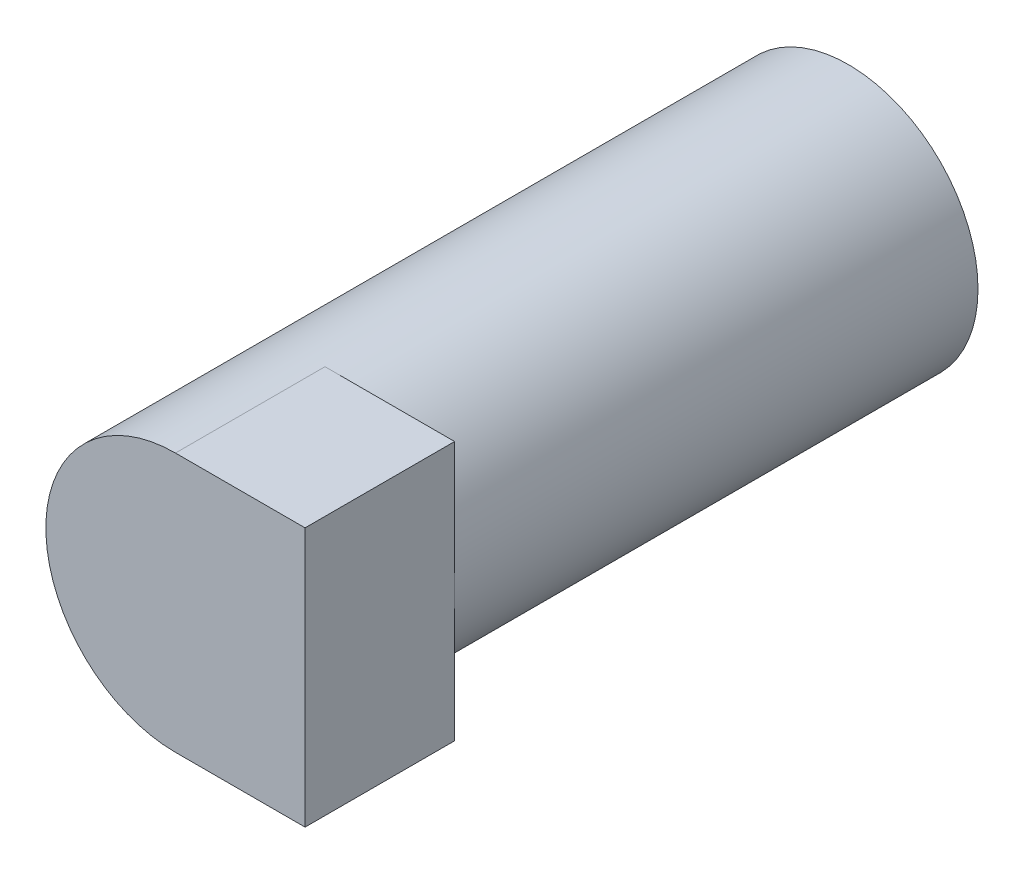
SolidWorks part; units mm, degrees
material "AISI 1045 Steel, cold drawn"
ref_plane "Front Plane" through (0, 0, 0) normal (0, 0, 1) x (1, 0, 0)
ref_plane "Top Plane" through (0, 0, 0) normal (0, 1, 0) x (1, 0, 0)
ref_plane "Right Plane" through (0, 0, 0) normal (1, 0, 0) x (0, 0, -1)
ref_axis "Axis1" through (0, 55, 0) along (0, -1, 0)
ref_axis "Axis2" through (88.99, 0, 0) along (-1, 0, 0)
ref_axis "Axis3" through (0, 0, -88.99) along (0, 0, 1)
sketch "Sketch1" plane through (0, 0, 0) normal (0, 0, 1) x (1, 0, 0)
  circle A0 centre (0, 0) radius 13
  dimension "D1" = 26
extrude "Boss-Extrude1" add sketch "Sketch1" along normal blind 67.5
sketch "Sketch2" plane through (0, 0, 0) normal (1, 0, 0) x (0, 0, -1)
  line L0 (-67.5, -13) -> (0, -13) construction
  line L1 (-67.5, 13) -> (-52.5, 13)
  line L2 (-67.5, 13) -> (-67.5, -13)
  line L3 (-67.5, -13) -> (-52.5, -13)
  line L4 (-52.5, 13) -> (-52.5, -13)
  dimension "D1" = 15
extrude "Boss-Extrude2" add sketch "Sketch2" along normal blind 13
